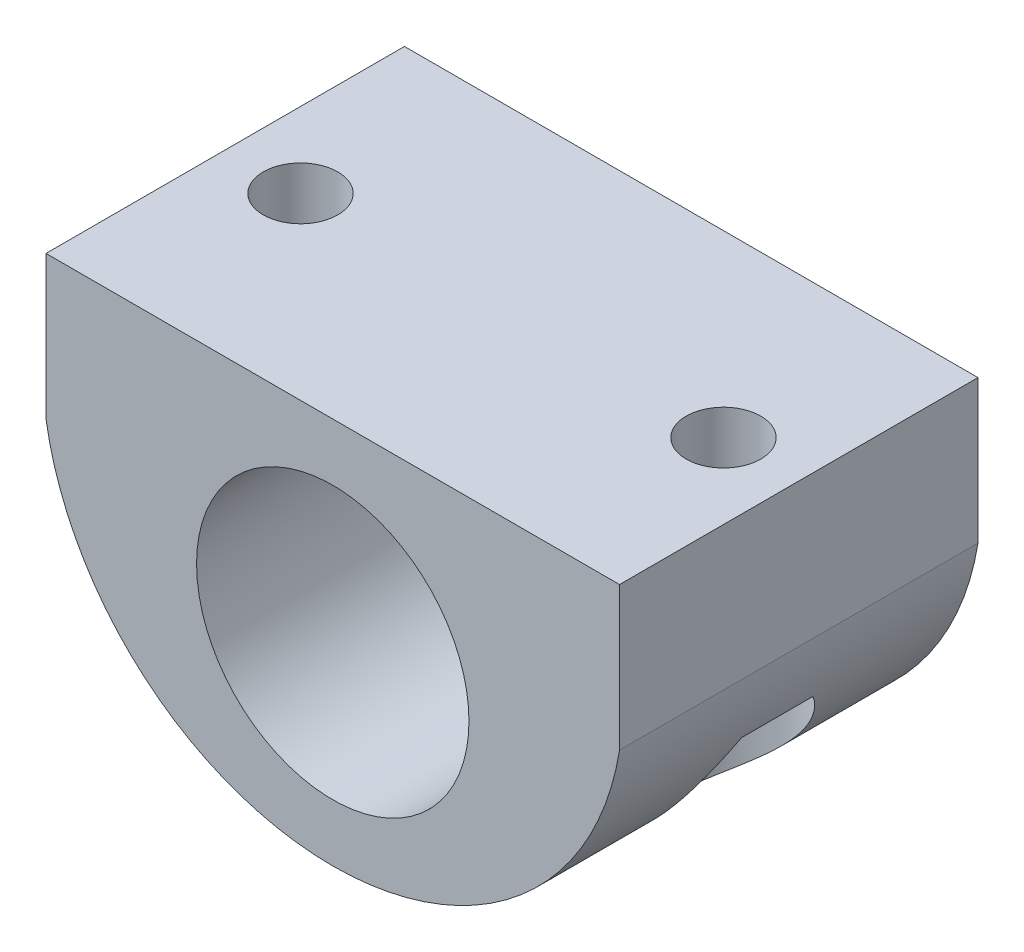
SolidWorks part; units mm, degrees
ref_plane "Alzado" through (0, 0, 0) normal (0, 0, 1) x (1, 0, 0)
ref_plane "Planta" through (0, 0, 0) normal (0, 1, 0) x (1, 0, 0)
ref_plane "Vista lateral" through (0, 0, 0) normal (1, 0, 0) x (0, 0, -1)
sketch "Croquis1" plane through (0, 0, 0) normal (0, 0, 1) x (1, 0, 0)
  line L0 (0, 13.5) -> (-20, 13.5)
  line L1 (-20, 13.5) -> (-20, 3.5)
  line L2 (0, 13.5) -> (20, 13.5)
  line L3 (20, 13.5) -> (20, 3.5)
  circle A0 centre (0, 0) radius 9.5
  arc A2 (-20, 3.5) -> (0, -13.5) centre (0, 6.7647) ccw
  arc A3 (0, -13.5) -> (20, 3.5) centre (0, 6.7647) ccw
  dimension "D1" = 19
  dimension "D3" = 20
  dimension "D4" = 20
  dimension "D5" = 10
  dimension "D6" = 10
extrude "Saliente-Extruir1" add sketch "Croquis1" along normal blind 25
sketch "Croquis2" plane through (0, 0, 0) normal (0, 0, -1) x (-1, 0, 0)
  line L3 (20, 13.5) -> (-20, 13.5)
  line L4 (-20, 13.5) -> (-20, 3.5)
  line L5 (20, 3.5) -> (20, 13.5)
  line L6 (20, 13.5) -> (-20, 13.5)
  line L7 (-20, 13.5) -> (-20, 3.5)
  line L8 (20, 3.5) -> (20, 13.5)
  arc A1 (-20, 3.5) -> (20, 3.5) centre (0, 6.7647) ccw
  arc A2 (-20, 3.5) -> (20, 3.5) centre (0, 6.7647) ccw
  dimension "D1" = 0
extrude "Saliente-Extruir2" add sketch "Croquis2" against normal blind 3
sketch "Croquis3" plane through (0, 13.5, 0) normal (0, 1, 0) x (1, 0, 0)
  line L0 (9.5, -25) -> (20, -25) construction
  line L1 (14.75, -25) -> (14.75, 0) construction
  line L2 (20, 0) -> (-20, 0) construction
  line L3 (-9.5, -25) -> (-20, -25) construction
  line L4 (20, -25) -> (-20, -25) construction
  line L5 (-14.75, -25) -> (-14.75, 0) construction
  circle A0 centre (14.75, -12.5) radius 2.6
  circle A1 centre (-14.75, -12.5) radius 2.6
  dimension "D1" = 5.2
  dimension "D2" = 5.2
extrude "Cortar-Extruir1" cut sketch "Croquis3" against normal blind 200 and the other way through all
ref_plane "Plano1" through (0, -11.5, 0) normal (0, 1, 0) x (1, 0, 0)
sketch "Croquis4" plane through (0, -11.5, 0) normal (0, 1, 0) x (1, 0, 0)
  circle A0 centre (-14.75, -12.5) radius 4.5
  circle A1 centre (14.75, -12.5) radius 4.5
  dimension "D1" = 9
  dimension "D2" = 9
extrude "Cortar-Extruir2" cut sketch "Croquis4" along normal blind 10
sketch "Croquis5" plane through (0, -11.5, 0) normal (0, 1, 0) x (1, 0, 0)
  line L0 (0, -25) -> (0, 0) construction
  line L1 (-20, -25) -> (20, -25) construction
  circle A0 centre (0, -12.5) radius 2
  dimension "D1" = 4
extrude "Cortar-Extruir3" cut sketch "Croquis5" along normal blind 10 and the other way blind 10
sketch "Croquis6" plane through (0, -11.5, 0) normal (0, 1, 0) x (1, 0, 0)
  circle A0 centre (0, -12.5) radius 4.5
  dimension "D1" = 9
extrude "Cortar-Extruir4" cut sketch "Croquis6" against normal blind 10.5 and the other way blind 0.5
